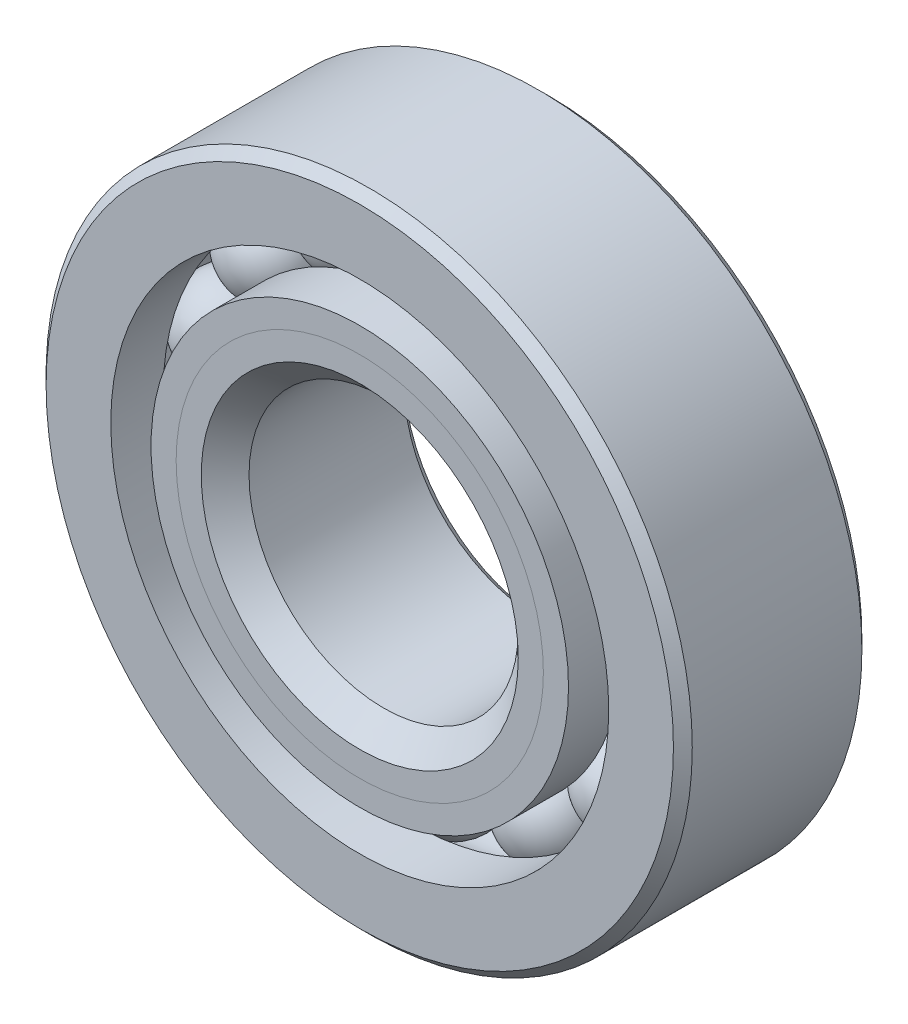
SolidWorks part; units mm, degrees
ref_plane "Front Plane" through (0, 0, 0) normal (0, 0, 1) x (1, 0, 0)
ref_plane "Top Plane" through (0, 0, 0) normal (0, 1, 0) x (1, 0, 0)
ref_plane "Right Plane" through (0, 0, 0) normal (1, 0, 0) x (0, 0, -1)
sketch "Sketch1" plane through (0, 0, 0) normal (1, 0, 0) x (0, 0, -1)
  line L0 (-5.5562, 0) -> (5.5562, 0) construction
  line L1 (0, 19.05) -> (0, -19.05) construction
  line L2 (5.0006, 19.05) -> (-5.0006, 19.05)
  line L3 (-5.0006, 19.05) -> (-5.5563, 18.4944)
  line L4 (-5.5563, 18.4944) -> (-5.5563, 14.68)
  line L5 (-5.5563, 14.68) -> (-2.4694, 14.68)
  line L6 (5.5563, 14.68) -> (2.4694, 14.68)
  line L7 (5.5563, 18.4944) -> (5.5563, 14.68)
  line L8 (5.0006, 19.05) -> (5.5563, 18.4944)
  line L9 (0, 19.05) -> (0, 13.4938) construction
  line L10 (0, 13.4938) -> (0, 7.9375) construction
  arc A0 (-2.4694, 14.68) -> (2.4694, 14.68) centre (0, 13.4938) cw
  point P14 (0, 7.9375)
  dimension "D3" = 4.9389
  dimension "D1" = 45
  dimension "Width" = 11.1125
  dimension "OD" = 38.1
  dimension "D2" = 0.5556
  dimension "Shaft Dia" = 15.875
  dimension "D4" = 1.1863
revolve "Revolve1" add sketch "Sketch1" angle 360 about L0
sketch "Sketch2" plane through (0, 0, 0) normal (1, 0, 0) x (0, 0, -1)
  line L0 (-5.5563, 12.3075) -> (-2.4694, 12.3075)
  line L1 (-5.5563, 18.4944) -> (-5.5563, -18.4944) construction
  line L2 (-5.5563, 12.3075) -> (-5.5563, 10.8267)
  line L3 (-5.5563, 10.8267) -> (-4.0754, 9.3458)
  line L4 (-4.0754, 9.3458) -> (0, 9.3458)
  line L5 (0, 19.05) -> (0, -19.05) construction
  line L6 (0, 9.3458) -> (0, 10.7542)
  line L7 (0, 10.7542) -> (0, 7.9375) construction
  line L8 (-5.5563, 12.3075) -> (-5.5563, 9.3458) construction
  line L9 (-5.5563, 9.3458) -> (-4.0754, 9.3458) construction
  arc A0 (-2.4694, 12.3075) -> (0, 10.7542) centre (0, 13.4938) ccw
  arc A1 (2.4694, 14.68) -> (-2.4694, 14.68) centre (0, 13.4938) ccw construction
  circle A2 centre (0, 13.4938) radius 2.7396 construction
  dimension "D1" = 45
revolve "Revolve2" add sketch "Sketch2" angle 360 about L0
sketch "Sketch3" plane through (0, 0, 0) normal (1, 0, 0) x (0, 0, -1)
  line L0 (-5.5563, 10.8267) -> (-4.0754, 9.3458)
  line L1 (-4.0754, 9.3458) -> (0, 9.3458)
  line L2 (0, 9.3458) -> (0, 10.7542)
  line L3 (-5.5563, 10.8267) -> (-5.5563, 9.3458)
  line L4 (-5.5563, 12.3075) -> (-5.5563, 9.3458) construction
  line L5 (-5.5563, 9.3458) -> (-4.1479, 7.9375)
  line L6 (-4.1479, 7.9375) -> (5.0006, 7.9375)
  line L7 (5.0006, 19.05) -> (5.0006, -19.05) construction
  line L8 (5.0006, 7.9375) -> (5.5563, 8.4931)
  line L9 (5.5563, -18.4944) -> (5.5563, 18.4944) construction
  line L10 (5.5563, 8.4931) -> (5.5563, 12.3075)
  line L11 (5.5563, 12.3075) -> (2.4694, 12.3075)
  line L13 (5.0006, 19.05) -> (5.5563, 18.4944) construction
  circle A0 centre (0, 13.4938) radius 2.7396 construction
  arc A1 (2.4694, 12.3075) -> (0, 10.7542) centre (0, 13.4938) cw
revolve "Revolve3" add sketch "Sketch3" angle 360 about L0
sketch "Sketch4" plane through (0, 0, 0) normal (1, 0, 0) x (0, 0, -1)
  line L0 (-2.7396, 13.4938) -> (2.7396, 13.4938)
  circle A1 centre (0, 13.4938) radius 2.7396 construction
  arc A2 (-2.7396, 13.4938) -> (2.7396, 13.4938) centre (0, 13.4938) cw
  arc A3 (2.4694, 14.68) -> (-2.4694, 14.68) centre (0, 13.4938) ccw construction
revolve "Revolve4" add sketch "Sketch4" angle 360 about L0
ref_axis "Axis1" through (0, 0, -5.5562) along (0, 0, 1)
pattern_circular "CirPattern1" count 14 every 25.714 about axis through (0, 0, -5.5562) along (0, 0, 1) of bodies 104
equation "\"D2@Sketch1\" = \"Width@Sketch1\"*.05"
equation "\"D3@Sketch1\" = \"Width@Sketch1\"/2.25"
equation "\"D4@Sketch1\" = (((\"OD@Sketch1\"-\"Width@Sketch1\")/2)/3.25)/3.5"
equation "\"D2@CirPattern1\" = 360/\"Balls@CirPattern1\""
